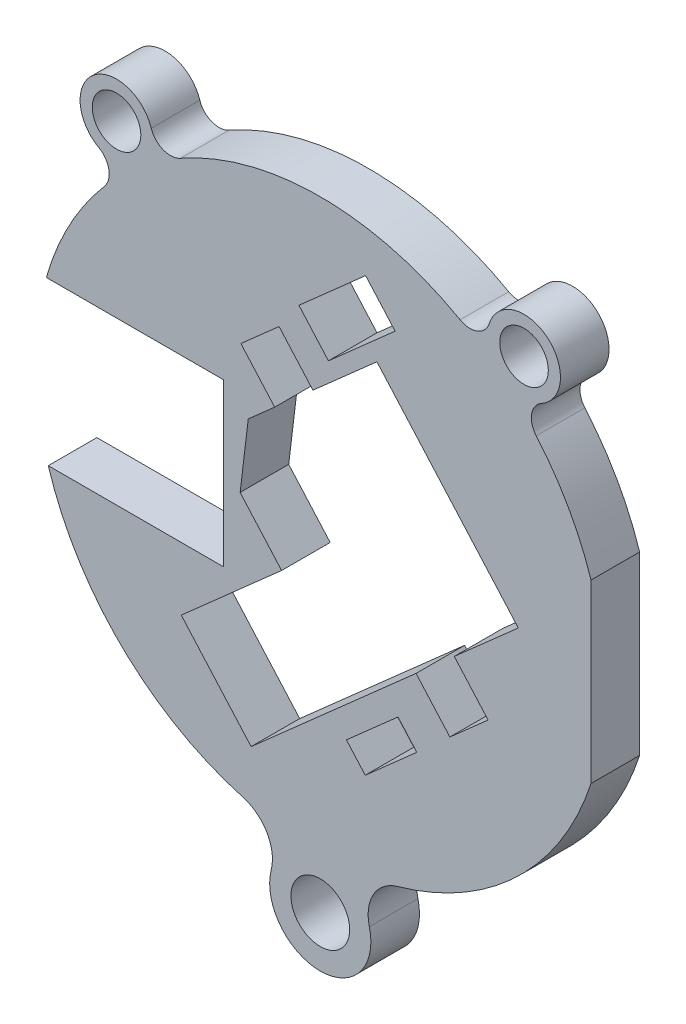
SolidWorks part; units mm, degrees
ref_plane "Front Plane" through (0, 0, 0) normal (0, 0, 1) x (1, 0, 0)
ref_plane "Top Plane" through (0, 0, 0) normal (0, 1, 0) x (1, 0, 0)
ref_plane "Right Plane" through (0, 0, 0) normal (1, 0, 0) x (0, 0, -1)
sketch "Sketch1" plane through (0, 0, 0) normal (0, 0, 1) x (1, 0, 0)
  line L0 (-21.141, 18.2245) -> (20.1141, 18.2245) construction
  line L1 (-4.8006, 1.8415) -> (-4.8006, -3.0861)
  line L2 (-4.8006, -3.0861) -> (-8.9662, -3.0861)
  line L3 (-8.9662, -3.0861) -> (-8.9662, -5.3514)
  line L4 (-8.9662, -5.3514) -> (-6.5786, -5.3514)
  line L5 (-4.9806, 7.3918) -> (-2.5835, 9.5123)
  line L6 (-2.5835, 9.5123) -> (-0.463, 7.1152)
  line L7 (-4.9806, 7.3918) -> (-2.8601, 4.9947)
  line L8 (3.2088, 10.3632) -> (-4.5153, 3.5306)
  line L9 (12.0777, 0.3371) -> (4.3536, -6.4955)
  line L10 (-4.5153, 3.5306) -> (-5.0276, -0.7207)
  line L11 (-5.0276, -0.7207) -> (0.0716, -6.4852)
  line L12 (0.0716, -6.4852) -> (4.3536, -6.4955)
  line L13 (-2.478, -3.6029) -> (7.6432, 5.3502) construction
  line L14 (3.2088, 10.3632) -> (12.0777, 0.3371)
  line L15 (3.2088, 10.3632) -> (11.8761, 18.0302)
  line L16 (-9.2588, -8.622) -> (-4.7522, -4.6355) construction
  line L17 (-9.2588, -8.622) -> (-5.994, -12.3128) construction
  line L18 (-4.7522, -4.6355) -> (-1.4874, -8.3263) construction
  line L19 (-5.994, -12.3128) -> (-1.4874, -8.3263) construction
  line L20 (12.0777, 0.3371) -> (20.228, 7.5468)
  line L21 (-6.5786, -5.3514) -> (-6.5786, -5.8039)
  line L22 (-6.5786, -5.8039) -> (-14.0208, -5.8039)
  line L23 (-14.0208, -5.8039) -> (-14.0208, 4.5593)
  line L24 (-14.0208, 4.5593) -> (-6.5786, 4.5593)
  line L25 (-6.5786, 4.5593) -> (-6.5786, 3.9924)
  line L26 (-6.5786, 3.9924) -> (-8.9662, 3.9924)
  line L27 (-8.9662, 3.9924) -> (-8.9662, 1.8415)
  line L28 (-8.9662, 1.8415) -> (-4.8006, 1.8415)
  line L29 (8.4059, -2.9109) -> (10.5264, -5.308)
  line L30 (10.5264, -5.308) -> (8.1292, -7.4285)
  line L31 (8.1292, -7.4285) -> (6.0088, -5.0313)
  line L32 (-4.7522, -4.6355) -> (-2.9639, -3.0536) construction
  line L33 (-1.4874, -8.3263) -> (0.5926, -6.4864) construction
  line L34 (-5.4555, -12.9216) -> (-0.9489, -8.9351)
  line L35 (-8.7203, -9.2308) -> (-4.2137, -5.2443)
  line L36 (-8.7203, -9.2308) -> (-5.4555, -12.9216)
  line L37 (-0.9489, -8.9351) -> (1.816, -6.4894)
  line L38 (-4.2137, -5.2443) -> (-2.4254, -3.6624)
  arc A0 (-15.2315, -0.5079) -> (3.302, 14.878) centre (0, 0) ccw construction
  circle A1 centre (0, 0) radius 21.59 construction
  circle A2 centre (0, 0) radius 21.59
  circle A3 centre (0, -18.415) radius 1.4224 construction
  circle A4 centre (0, 18.415) radius 1.4224 construction
  circle A5 centre (0, -18.415) radius 1.4224
  circle A6 centre (0, 18.415) radius 1.4224
  circle A7 centre (0, 0) radius 15.24
  dimension "D3" = 30.48
  dimension "D1" = 33.4645
  dimension "D2" = 20.0406
  dimension "D4" = 4.9276
  dimension "D5" = 2.7178
  dimension "D6" = 8.7122
  dimension "D7" = 7.8613
  dimension "D8" = 2.7178
  dimension "D9" = 3.2004
  dimension "D10" = 13.3858
  dimension "D11" = 3.1623
  dimension "D12" = 10.3124
  dimension "D13" = 8.6106
  dimension "D14" = 7.6962
  dimension "D15" = 6.0168
  dimension "D16" = 2.3876
  dimension "D17" = 4.9276
  dimension "D18" = 22.86
  dimension "D19" = 7.4422
  dimension "D20" = 5.0546
  dimension "D21" = 13.6652
  dimension "D22" = 29.2608
  dimension "D23" = 0.8128
extrude "Boss-Extrude1" add sketch "Sketch1" along normal blind 3.048 contours L15 A7 L20 L9 L29 L30 L31 L12 L33 L19 L17 L16 L32 L11 L1 L2 L3 L4 L21 L22 L23 L24 L25 L26 L27 L28 L10 L8 L7 L5 L6 | L28 L27 L26 L25 L24 L23 L22 L21 L4 L3 L2 L1 L11 L10 | A7 L15 A2 L20 A6 A5 region at (-6.8834, 2.2726, 0) region at (-10.1343, -0.6067, 0) region at (-13.5004, -8.3055, 0)
sketch "Sketch2" plane through (0, 0, 3.048) normal (0, 0, 1) x (1, 0, 0)
  line L0 (-5.0276, 2.3876) -> (-5.0276, -2.794)
  line L1 (-5.0276, 2.3876) -> (-10.4871, 2.3876)
  line L2 (-10.4871, 2.3876) -> (-10.4871, 3.8608)
  line L3 (-10.4871, 3.8608) -> (-7.085, 3.8608)
  line L4 (-7.085, 3.8608) -> (-7.085, 4.8768)
  line L5 (-7.085, 4.8768) -> (-14.4764, 4.8768)
  line L6 (-14.4764, 4.8768) -> (-14.4764, -5.2832)
  line L7 (-14.4764, -5.2832) -> (-7.085, -5.2832)
  line L8 (-7.085, -5.2832) -> (-7.085, -4.2672)
  line L9 (-7.085, -4.2672) -> (-10.4871, -4.2672)
  line L10 (-10.4871, -4.2672) -> (-10.4871, -2.794)
  line L11 (-10.4871, -2.794) -> (-5.0276, -2.794)
  line L12 (-5.0276, 2.3876) -> (-4.653, 2.3876)
  line L13 (-4.5153, 3.5306) -> (-5.0276, -0.7207) construction
  line L14 (-5.0276, -2.794) -> (-3.1935, -2.794)
  line L15 (-5.0276, -0.7207) -> (-2.4254, -3.6624) construction
  line L16 (-7.085, 3.8608) -> (-7.085, -4.2672)
  line L17 (-14.4764, 4.8768) -> (-21.032, 4.8768)
  line L18 (-14.4764, -5.2832) -> (-20.9336, -5.2832)
  arc A0 (11.8761, 18.0302) -> (20.228, 7.5468) centre (0, 0) ccw construction
  arc M2 (11.8761, 18.0302) -> (20.228, 7.5468) centre (0, 0) ccw
  dimension "D1" = 9.4488
  dimension "D2" = 7.3914
  dimension "D3" = 10.16
  dimension "D4" = 1.016
  dimension "D5" = 5.1816
  dimension "D6" = 5.4596
  dimension "D7" = 1.4732
  dimension "D8" = 1.143
extrude "Cut-Extrude3" cut sketch "Sketch2" against normal through all contours L10 L11 L0 L1 L2 L3 L4 L5 L6 L7 L8 L9 | L16 L3 L2 L1 | L16 L11 L10 L9 | L18 L6 L17 M2 region at (-11.0879, -0.2032, 3.048) region at (-8.7861, 3.1242, 3.048) region at (-8.7861, -3.5306, 3.048) region at (-17.9346, -0.1913, 3.048)
sketch "Sketch3" plane through (0, 0, 0) normal (0, 0, -1) x (-1, 0, 0)
  line L0 (-20.8712, -5.5245) -> (-16.9841, -5.5245)
  line L1 (-16.9841, -5.5245) -> (-20.8712, -5.5245) construction
  line L2 (-16.9841, -5.5245) -> (-16.9841, 4.6772)
  line L3 (-8.4059, -2.9109) -> (-20.228, 7.5468) construction
  line L4 (-16.9841, 5.5245) -> (-16.9841, -5.5245) construction
  line L5 (-16.9841, 4.6772) -> (-20.228, 7.5468)
  arc A0 (-20.228, 7.5468) -> (20.9336, -5.2832) centre (0, 0) ccw construction
  arc A1 (-20.228, 7.5468) -> (-20.8712, -5.5245) centre (0, 0) ccw
  arc A2 (-20.8712, -5.5245) -> (-20.8712, 5.5245) centre (0, 0) ccw construction
extrude "Cut-Extrude4" cut sketch "Sketch3" against normal through all
sketch "Sketch4" plane through (0, 0, 0) normal (0, 0, -1) x (-1, 0, 0)
  line L0 (-12.3201, -16.1591) -> (12.3201, 16.1591) construction
  line L1 (-13.8351, -15.0041) -> (10.8052, 17.3141)
  line L2 (-10.8052, -17.3141) -> (13.8351, 15.0041)
  line L3 (-16.1591, 12.3201) -> (16.1591, -12.3201) construction
  line L4 (-15.0041, 13.8351) -> (17.3141, -10.8052)
  line L5 (-17.3141, 10.8052) -> (15.0041, -13.8351)
  line L6 (-16.9841, 5.5245) -> (-16.9841, 4.6772)
  line L7 (-16.9841, 4.6772) -> (-12.4201, 0.64)
  line L8 (-8.4059, -2.9109) -> (-16.9841, 4.6772) construction
  line L9 (-12.4201, 0.64) -> (-3.5512, 10.6661)
  line L10 (0.463, 7.1152) -> (-11.8761, 18.0302) construction
  line L11 (-3.5512, 10.6661) -> (-8.9594, 15.4501)
  line L12 (5.0276, -0.7207) -> (2.4254, -3.6624) construction
  line L13 (0, 0) -> (2.7145, -20.1379) construction
  line L14 (1.8879, 0.2545) -> (4.6025, -19.8834)
  line L15 (-1.8879, -0.2545) -> (0.8266, -20.3924)
  line L16 (-16.1591, 12.3201) -> (12.3201, 16.1591) construction
  circle A0 centre (0, 0) radius 17.86
  arc A1 (-13.8351, -15.0041) -> (-10.8052, -17.3141) centre (-12.3201, -16.1591) ccw
  arc A2 (13.8351, 15.0041) -> (10.8052, 17.3141) centre (12.3201, 16.1591) ccw
  arc A3 (-15.0041, 13.8351) -> (-17.3141, 10.8052) centre (-16.1591, 12.3201) ccw
  arc A4 (15.0041, -13.8351) -> (17.3141, -10.8052) centre (16.1591, -12.3201) ccw
  circle A5 centre (12.3201, 16.1591) radius 1.1049
  circle A6 centre (16.1591, -12.3201) radius 1.1049
  circle A7 centre (-12.3201, -16.1591) radius 1.1049
  circle A8 centre (-16.1591, 12.3201) radius 1.1049
  arc A9 (1.8879, 0.2545) -> (-1.8879, -0.2545) centre (0, 0) ccw
  arc A10 (0.8266, -20.3924) -> (4.6025, -19.8834) centre (2.7145, -20.1379) ccw
  arc A11 (2.7145, -20.1379) -> (16.1591, -12.3201) centre (0, 0) ccw construction
  circle A12 centre (2.7145, -20.1379) radius 1.1049
  point P6 (0, 0)
  point P13 (0, 0)
  point P39 (1.3573, -10.0689)
  line M1 (-8.4059, -2.9109) -> (-16.9841, 4.6772)
  line M3 (-16.9841, -5.5245) -> (-20.8712, -5.5245)
  arc M4 (-20.8712, -5.5245) -> (20.9336, -5.2832) centre (0, 0) ccw
  line M5 (20.9336, -5.2832) -> (7.085, -5.2832)
  line M7 (7.085, 4.8768) -> (21.032, 4.8768)
  arc M8 (21.032, 4.8768) -> (-11.8761, 18.0302) centre (0, 0) ccw
  line M9 (-11.8761, 18.0302) -> (0.463, 7.1152)
  circle M24 centre (0, 18.415) radius 1.4224
  circle M25 centre (0, -18.415) radius 1.4224
  dimension "D1" = 3.81
  dimension "D2" = 3.81
  dimension "D3" = 13.97
extrude "Boss-Extrude2" add sketch "Sketch4" against normal up to vertex (3.048 mm away) contours A0 L4 L9 M9 | L4 A0 L5 L9 | L5 A0 L6 L9 M1 | L4 A3 L5 A0 A8 | A2 L1 A0 L2 A5 M8 | A0 M24 | A0 M25 | A0 L15 M25 | L15 A0 M25 | A10 M4 | A2 M8 region at (13.4131, 4.8762, 0) region at (10.9588, 8.3691, 0) region at (16.2523, 10.0852, 0) region at (0.2829, -17.4804, 0) region at (-2.9174, -21.6425, 0) region at (8.1323, 11.4955, 0) region at (-0.7535, -17.5272, 0) region at (-0.9598, -18.5708, 0) region at (-10.0849, 16.2525, 0) region at (0, 17.4932, 0) region at (-13.2407, 17.3665, 0) up to point (10.5264, -5.308, 3.048)
extrude "Cut-Extrude5" cut sketch "Sketch4<3>" against normal through all contours A4 L5 A0 L2 A1 M25 M4 | A4 A0 L4 M4 M5 | A1 L1 A0 M3 M4 | A7 | A6 | A5 | A2 L2 A0 M7 M8 | A2 A0 L1 M8 M9 M24 | L1 A1 L2 A0 A7 M4 | A10 A4 L5 A0 L14 M4 | A4 L4 A0 L5 A6 M4 | A12 region at (16.6582, -10.306, 0) region at (13.002, -14.0284, 0) region at (5.4053, -18.8788, 0) region at (-9.8123, -16.8747, 0) region at (-5.4955, 17.2518, 0) region at (-15.6105, -14.0703, 0) region at (-16.798, 10.0037, 0) region at (-18.1332, -7.9591, 0) region at (-12.3201, 16.1591, 0) region at (-16.1591, -12.3201, 0) region at (12.3201, -16.1591, 0) region at (-2.7145, -20.1379, 0)
sketch "Sketch4<3>" plane through (0, 0, 0) normal (0, 0, -1) x (-1, 0, 0) same geometry as "Sketch4"
sketch "Sketch5" plane through (0, 0, 3.048) normal (0, 0, 1) x (1, 0, 0)
  line L0 (4.3536, -6.4955) -> (-4.3384, -14.1843)
  line L1 (-4.3384, -14.1843) -> (-5.4555, -12.9216)
  line L2 (-8.7203, -9.2308) -> (-5.4555, -12.9216) construction
  line L3 (6.0088, -5.0313) -> (4.3536, -6.4955) construction
  line L4 (-5.4555, -12.9216) -> (1.816, -6.4894)
  line L5 (1.816, -6.4894) -> (4.3536, -6.4955)
extrude "Cut-Extrude10" cut sketch "Sketch5" against normal through all
sketch "Sketch6" plane through (0, 0, 3.048) normal (0, 0, 1) x (1, 0, 0)
  line L0 (17.3141, 10.8052) -> (15.2768, 9.2519) construction
  line L1 (15.0041, 13.8351) -> (12.9668, 12.2818) construction
  line L2 (17.3141, 10.8052) -> (15.2768, 9.2519)
  line L3 (15.0041, 13.8351) -> (12.9668, 12.2818)
  line L4 (17.5451, 10.5023) -> (15.472, 8.9216)
  line L5 (14.7731, 14.138) -> (12.7, 12.5574)
  line L23 (-4.9801, -19.8325) -> (-4.6378, -17.2935)
  line L24 (-0.1068, -17.9043) -> (-0.449, -20.4433)
  line L25 (-4.9801, -19.8325) -> (-4.6318, -17.2489)
  line L26 (-0.1008, -17.8597) -> (-0.449, -20.4433)
  line L29 (14.7731, 14.138) -> (12.7358, 12.5847) construction
  line L30 (17.5451, 10.5023) -> (15.5078, 8.9489) construction
  line L31 (-14.138, 14.7731) -> (-12.5847, 12.7358)
  line L32 (-8.9489, 15.5078) -> (-10.5023, 17.5451)
  line L33 (-14.138, 14.7731) -> (-12.5574, 12.7)
  line L34 (-8.9216, 15.472) -> (-10.5023, 17.5451)
  arc A0 (17.3141, 10.8052) -> (15.0041, 13.8351) centre (16.1591, 12.3201) ccw construction
  arc A1 (17.3141, 10.8052) -> (15.0041, 13.8351) centre (16.1591, 12.3201) ccw
  arc A2 (17.5451, 10.5023) -> (14.7731, 14.138) centre (16.1591, 12.3201) ccw
  arc A11 (-4.9801, -19.8325) -> (-0.449, -20.4433) centre (-2.7145, -20.1379) ccw
  arc A12 (-4.9801, -19.8325) -> (-0.449, -20.4433) centre (-2.7145, -20.1379) ccw
  circle A14 centre (0, 0) radius 17.86
  arc A15 (-10.5023, 17.5451) -> (-14.138, 14.7731) centre (-12.3201, 16.1591) ccw
  arc A16 (-10.5023, 17.5451) -> (-14.138, 14.7731) centre (-12.3201, 16.1591) ccw
  line M25 (-4.2602, -17.3444) -> (-4.6025, -19.8834)
  arc M26 (-4.6025, -19.8834) -> (-0.8266, -20.3924) centre (-2.7145, -20.1379) ccw
  line M27 (-0.8266, -20.3924) -> (-0.4844, -17.8534)
  arc M28 (-0.4844, -17.8534) -> (16.9841, -5.5245) centre (0, 0) ccw
  arc M30 (16.9841, 5.5245) -> (15.2768, 9.2519) centre (0, 0) ccw
  line M31 (15.2768, 9.2519) -> (17.3141, 10.8052)
  arc M32 (17.3141, 10.8052) -> (15.0041, 13.8351) centre (16.1591, 12.3201) ccw
  line M33 (15.0041, 13.8351) -> (12.9668, 12.2818)
  arc M34 (12.9668, 12.2818) -> (-9.2519, 15.2768) centre (0, 0) ccw
  line M35 (-9.2519, 15.2768) -> (-10.8052, 17.3141)
  arc M36 (-10.8052, 17.3141) -> (-13.8351, 15.0041) centre (-12.3201, 16.1591) ccw
  line M37 (-13.8351, 15.0041) -> (-12.2818, 12.9668)
  arc M38 (-12.2818, 12.9668) -> (-17.1812, 4.8768) centre (0, 0) ccw
  arc M42 (-17.0607, -5.2832) -> (-4.2602, -17.3444) centre (0, 0) ccw
  dimension "D1" = 0.381
  dimension "D2" = 0.381
  dimension "D3" = 0.381
extrude "Boss-Extrude3" add sketch "Sketch6" against normal up to vertex contours L34 A16 L33 M38 M37 M36 M35 M34 | L25 A12 L26 M28 M27 M26 M25 M42 | L4 A2 L5 M34 M33 M32 M31 M30 region at (17.7383, 13.5242, 3.048) region at (-9.1284, 15.4449, 3.048) region at (-0.1744, -17.8725, 3.048) up to point (8.4059, -2.9109, 0)
sketch "Sketch7" plane through (0, 0, 0) normal (0, 0, -1) x (-1, 0, 0)
  line L0 (7.085, 4.8768) -> (6.0563, 4.8768)
  line L1 (6.0563, 4.8768) -> (6.0563, -5.2832)
  line L2 (6.0563, -5.2832) -> (7.085, -5.2832)
  line L3 (5.0276, -0.7207) -> (7.085, -0.7207) construction
  line L4 (7.085, 4.8768) -> (7.085, -5.2832) construction
  line L5 (7.085, 4.8768) -> (7.085, -5.2832)
  point P11 (6.0563, -0.7207)
extrude "Cut-Extrude11" cut sketch "Sketch7" against normal through all
sketch "Sketch8" plane through (0, 0, 3.048) normal (0, 0, 1) x (1, 0, 0)
  circle A0 centre (0, 0) radius 17.86
  circle A1 centre (0, 0) radius 23.4976
extrude "Cut-Extrude12" cut sketch "Sketch8" against normal through all
sketch "Sketch9" plane through (0, 0, 3.048) normal (0, 0, 1) x (1, 0, 0)
  line L0 (0, 17.86) -> (-14.5094, 17.86) construction
  circle A0 centre (12.7793, 15.574) radius 1.524
  circle A1 centre (12.7793, 15.574) radius 2.286
  circle A2 centre (14.5094, 12.4672) radius 1.27
  circle A3 centre (9.3946, 16.6642) radius 1.27
  circle A4 centre (-12.7793, 15.574) radius 2.286
  circle A5 centre (-9.3946, 16.6642) radius 1.27
  circle A6 centre (-14.5094, 12.4672) radius 1.27
  circle A7 centre (0, -21.035) radius 1.8415
  circle A8 centre (0, -21.035) radius 3.175
  circle A9 centre (5.5404, -19.6332) radius 2.54
  circle A10 centre (-5.5404, -19.6332) radius 2.54
  circle A11 centre (-12.7793, 15.574) radius 1.524
  circle A12 centre (0, 0) radius 17.86
  circle A13 centre (0, 0) radius 17.86
  arc A14 (16.9841, 5.5245) -> (-17.1812, 4.8768) centre (0, 0) ccw construction
  arc M17 (16.9841, 5.5245) -> (-17.1812, 4.8768) centre (0, 0) ccw
  arc M21 (-17.0607, -5.2832) -> (16.9841, -5.5245) centre (0, 0) ccw
  dimension "D1" = 3.048
  dimension "D2" = 4.572
  dimension "D3" = 2.54
  dimension "D4" = 2.54
  dimension "D5" = 3.683
  dimension "D6" = 6.35
  dimension "D7" = 5.08
extrude "Boss-Extrude4" add sketch "Sketch9" against normal up to vertex contours A2 A1 M17 | A1 A0 | A3 A1 M17 | A6 A4 M17 | A4 A11 | A5 A4 M17 | A8 A7 | A10 A8 M21 | A9 A8 M21 region at (14.6944, 14.4484, 3.048) region at (10.1667, 15.1037, 3.048) region at (12.8282, 12.9198, 3.048) region at (-10.1667, 15.1037, 3.048) region at (-10.5849, 15.9187, 3.048) region at (-12.8282, 12.9198, 3.048) region at (2.6103, -18.2487, 3.048) region at (3.0615, -20.6537, 3.048) region at (-2.6103, -18.2487, 3.048) up to point (-0.463, 7.1152, 0)
sketch "Sketch10" plane through (0, 0, 3.048) normal (0, 0, 1) x (1, 0, 0)
  circle A0 centre (-10.8325, -7.6454) radius 1.143
  circle A1 centre (0, -13.2588) radius 1.143
  circle A2 centre (8.579, 10.1092) radius 1.143
  dimension "D1" = 2.286
extrude "Cut-Extrude13" [suppressed] cut sketch "Sketch10" against normal through all
sketch "Sketch11" plane through (0, 0, 3.048) normal (0, 0, 1) x (1, 0, 0)
  line L0 (-1.341, 11.2896) -> (0.5102, 9.1969)
  line L1 (0.5102, 9.1969) -> (4.6956, 12.8993)
  line L2 (4.6956, 12.8993) -> (2.8445, 14.992)
  line L3 (2.8445, 14.992) -> (-1.341, 11.2896)
  line L5 (-2.5835, 9.5123) -> (-0.463, 7.1152) construction
  line L6 (6.0533, -9.2987) -> (2.8191, -12.1596)
  line L7 (2.8191, -12.1596) -> (1.6411, -10.8279)
  line L8 (1.6411, -10.8279) -> (4.8753, -7.967)
  line L9 (4.8753, -7.967) -> (6.0533, -9.2987)
  line L10 (-4.9806, 7.3918) -> (-2.5835, 9.5123) construction
  line L11 (8.1292, -7.4285) -> (6.0088, -5.0313) construction
  line L12 (10.5264, -5.308) -> (8.1292, -7.4285) construction
  point P6 (-1.5232, 8.3137)
  dimension "D1" = 2.794
  dimension "D2" = 2.1082
  dimension "D3" = 5.588
  dimension "D4" = 1.778
  dimension "D5" = 4.318
  dimension "D6" = 2.794
  dimension "D7" = 0.0254
  dimension "D8" = 0.508
extrude "Cut-Extrude14" cut sketch "Sketch11" against normal through all
sketch "Sketch13" plane through (0, 0, 3.048) normal (0, 0, 1) x (1, 0, 0)
  line B0 (-6.0563, 4.8768) -> (-17.1812, 4.8768)
  line B1 (-6.0563, 4.8768) -> (-6.0563, -5.2832)
  line B2 (-17.0607, -5.2832) -> (-6.0563, -5.2832)
  line B3 (-8.7203, -9.2308) -> (-2.4254, -3.6624)
  line B4 (-8.7203, -9.2308) -> (-4.3384, -14.1843)
  line B5 (6.0088, -5.0313) -> (-4.3384, -14.1843)
  line B6 (1.6411, -10.8279) -> (2.8023, -12.1406)
  line B7 (4.8753, -7.967) -> (1.6411, -10.8279)
  line B8 (2.8023, -12.1406) -> (6.0365, -9.2797)
  line B9 (6.0365, -9.2797) -> (4.8753, -7.967)
  line B10 (8.1292, -7.4285) -> (6.0088, -5.0313)
  line B11 (10.5264, -5.308) -> (8.1292, -7.4285)
  line B12 (8.4059, -2.9109) -> (10.5264, -5.308)
  line B13 (8.4059, -2.9109) -> (12.4201, 0.64)
  line B14 (12.4201, 0.64) -> (3.5512, 10.6661)
  line B15 (-0.463, 7.1152) -> (3.5512, 10.6661)
  line B16 (-2.5835, 9.5123) -> (-0.463, 7.1152)
  line B17 (-4.9806, 7.3918) -> (-2.5835, 9.5123)
  line B18 (-4.9806, 7.3918) -> (-2.8601, 4.9947)
  line B19 (-2.8601, 4.9947) -> (-4.5153, 3.5306)
  line B20 (-4.5153, 3.5306) -> (-5.0276, -0.7207)
  line B21 (-5.0276, -0.7207) -> (-2.4254, -3.6624)
  line B22 (-1.0044, 10.9091) -> (0.8468, 8.8164)
  line B23 (3.181, 14.6115) -> (-1.0044, 10.9091)
  line B24 (5.0322, 12.5188) -> (3.181, 14.6115)
  line B25 (0.8468, 8.8164) -> (5.0322, 12.5188)
  line B26 (16.9841, -5.5245) -> (16.9841, 5.5245)
  circle B27 centre (-10.8325, -7.6454) radius 1.143
  circle B28 centre (0, -13.2588) radius 1.143
  circle B29 centre (8.579, 10.1092) radius 1.143
sketch_block_instance "Block1-1"
sketch_block "Block1"
